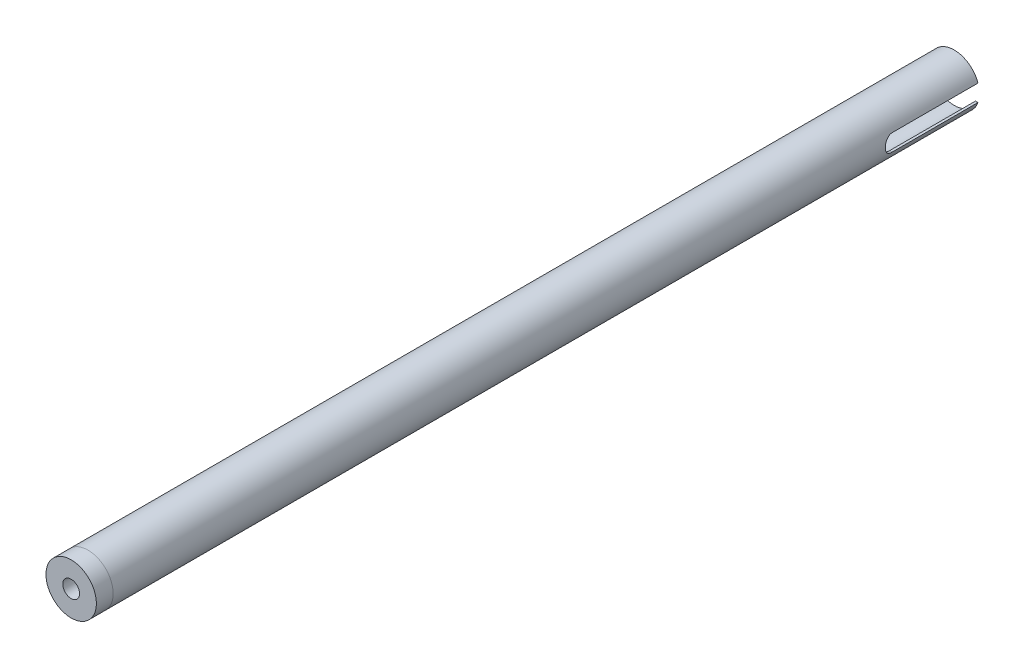
SolidWorks part; units mm, degrees
material "AISI 4130 Steel, normalized at 870C"
ref_plane "Front Plane" through (0, 0, 0) normal (0, 0, 1) x (1, 0, 0)
ref_plane "Top Plane" through (0, 0, 0) normal (0, 1, 0) x (1, 0, 0)
ref_plane "Right Plane" through (0, 0, 0) normal (1, 0, 0) x (0, 0, -1)
sketch "Axis" plane through (0, 0, 0) normal (0, 1, 0) x (1, 0, 0)
  line L0 (0, 0) -> (0, 333.5734) construction
  line L1 (0, 0) -> (0, -21.9075) construction
  line L2 (0, 333.5734) -> (-9.525, 333.5734) construction
  line L3 (0, 368.0751) -> (-10.3188, 330.6983) construction
  dimension "D1" = 21.9075
  dimension "D2" = 9.525
sketch "Sketch1" plane through (0, 0, 0) normal (0, 0, 1) x (1, 0, 0)
  line L0 (-9.525, 0) -> (9.525, 0) construction
  line L1 (-8.9803, 3.175) -> (8.9803, 3.175)
  line L2 (-8.9803, -3.175) -> (8.9803, -3.175)
  circle A0 centre (0, 0) radius 9.525
  circle A1 centre (0, 0) radius 8.636
  circle A2 centre (0, 0) radius 3.175
  dimension "D1" = 19.05
  dimension "D3" = 6.35
  dimension "D2" = 0.889
  dimension "D4" = 6.35
extrude "Threaded insert 1-1" add sketch "Sketch1" against normal blind 6.35 contours A2 L1 A1 | A1 L1 A0 | A2 L0 A1 L1 | A1 L0 A0 L1 | L0 A1 L2 A0 | L0 A2 L2 A1 | A2 L2 A1 | A1 L2 A0 | L0 A1 L2 A2 | L0 A0 L2 A1 | A0 L0 A1 L1 | A1 L0 A2 L1 region at (5.4259, 1.6615, 0) region at (5.4259, -1.6615, 0) region at (8.8881, 1.6046, 0) region at (8.8881, -1.6046, 0) region at (-5.4259, -1.6615, 0) region at (-5.4259, 1.6615, 0) region at (0, 5.4321, 0) region at (0, -5.4321, 0) region at (0, 8.8265, 0) region at (8.5057, -3.3655, 0) region at (-8.8881, -1.6046, 0) region at (-8.8881, 1.6046, 0)
extrude "Threaded insert 1-2" add sketch "Sketch1<3>" against normal blind 6.35 from surface contours A2 L1 A1 | A2 L0 A1 L1 | L0 A2 L2 A1 | A2 L2 A1 | L0 A1 L2 A2 | A1 L0 A2 L1 region at (5.4259, 1.6615, 0) region at (5.4259, -1.6615, 0) region at (-5.4259, -1.6615, 0) region at (-5.4259, 1.6615, 0) region at (0, 5.4321, 0) region at (0, -5.4321, 0) starting at face at (9.525, 0, -6.35)
sketch "Sketch1<3>" plane through (0, 0, 0) normal (0, 0, 1) x (1, 0, 0) same geometry as "Sketch1"
extrude "A-arm tube" add sketch "Sketch1<4>" against normal up to vertex (333.5734 mm away) from surface separate body contours A1 L1 A0 | A1 L0 A0 L1 | L0 A1 L2 A0 | A1 L2 A0 | L0 A0 L2 A1 | A0 L0 A1 L1 region at (8.8881, 1.6046, 0) region at (8.8881, -1.6046, 0) region at (0, 8.8265, 0) region at (8.5057, -3.3655, 0) region at (-8.8881, -1.6046, 0) region at (-8.8881, 1.6046, 0) up to point (0, 0, -333.5734) starting at face at (8.636, 0, -6.35)
sketch "Sketch1<4>" plane through (0, 0, 0) normal (0, 0, 1) x (1, 0, 0) same geometry as "Sketch1"
extrude "Apex slot" cut sketch "Sketch1<5>" along normal blind 35.56 from surface contours A0 L0 A1 L1 | L0 A0 L2 A1 | A1 L0 A0 L1 | L0 A1 L2 A0 region at (8.8881, 1.6046, 0) region at (8.8881, -1.6046, 0) region at (-8.8881, -1.6046, 0) region at (-8.8881, 1.6046, 0) starting at face at (8.636, 0, -333.5734)
sketch "Sketch1<5>" plane through (0, 0, 0) normal (0, 0, 1) x (1, 0, 0) same geometry as "Sketch1"
fillet "Fillet1" radius 3.175 4 edges at (-8.5057, 3.175, -298.0134) (-8.5057, -3.175, -298.0134) (8.5057, -3.175, -298.0134) (8.5057, 3.175, -298.0134)
equation "\"tube diameter\"= 3 / 4"
equation "\"tube thickness\"= .035"
equation "\"apex thickness\"= .25"
equation "\"tube slot\"= 1.4"
equation "\"D1@Sketch1\"=\"tube diameter\""
equation "\"D2@Sketch1\"=\"tube thickness\""
equation "\"threaded insert hole\"= 1 / 4"
equation "\"D3@Sketch1\"=\"threaded insert hole\""
equation "\"D4@Sketch1\"=\"apex thickness\""
equation "\"D1@Apex slot\" = \"tube slot\""
equation "\"D1@Fillet1\"=\"apex thickness\"/2"
equation "\"D2@Axis\"=\"tube diameter\"/2"
